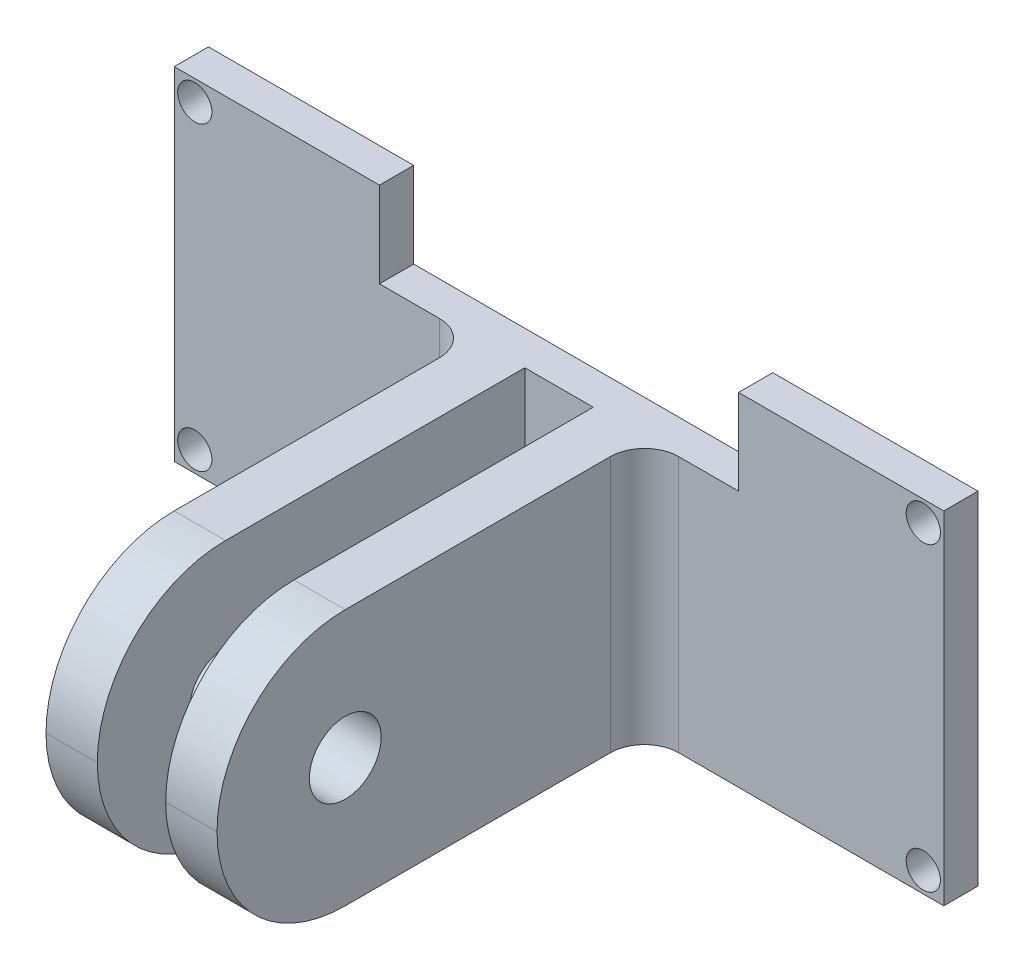
SolidWorks part; units mm, degrees
ref_plane "前视基准面" through (0, 0, 0) normal (0, 0, 1) x (1, 0, 0)
ref_plane "上视基准面" through (0, 0, 0) normal (0, 1, 0) x (1, 0, 0)
ref_plane "右视基准面" through (0, 0, 0) normal (1, 0, 0) x (0, 0, -1)
sketch "草图1" plane through (0, 0, 0) normal (0, 0, 1) x (1, 0, 0)
  line L0 (1.4667, 10.9333) -> (13.4667, 10.9333)
  line L2 (-31.5333, 10.9333) -> (-19.5333, 10.9333)
  line L3 (-31.5333, 10.9333) -> (-31.5333, -9.0667)
  line L4 (-31.5333, -9.0667) -> (13.4667, -9.0667)
  line L5 (13.4667, 10.9333) -> (13.4667, -9.0667)
  line L6 (-19.5333, 10.9333) -> (-19.5333, 5.9333)
  line L7 (-19.5333, 5.9333) -> (1.4667, 5.9333)
  line L8 (1.4667, 10.9333) -> (1.4667, 5.9333)
  circle A0 centre (-30.3333, 9.7333) radius 1
  circle A1 centre (-30.3333, -7.8667) radius 1
  circle A2 centre (12.2667, 9.7333) radius 1
  circle A3 centre (12.2667, -7.8667) radius 1
  point P16 (1.4667, 8.4333)
  dimension "D11" = 2
  dimension "D12" = 2
  dimension "D13" = 2
  dimension "D14" = 2
  dimension "D1" = 45
  dimension "D2" = 20
  dimension "D3" = 1.2
  dimension "D4" = 1.2
  dimension "D5" = 1.2
  dimension "D6" = 1.2
  dimension "D7" = 1.2
  dimension "D8" = 1.2
  dimension "D9" = 1.2
  dimension "D10" = 1.2
  dimension "D15" = 12
  dimension "D16" = 12
extrude "凸台-拉伸1" add sketch "草图1" along normal blind 2
sketch "草图2" plane through (0, 0, 2) normal (0, 0, 1) x (1, 0, 0)
  line L2 (-14.0333, 5.9333) -> (-14.0333, -9.0667)
  line L3 (-14.0333, -9.0667) -> (-11.0333, -9.0667)
  line L4 (-11.0333, 5.9333) -> (-11.0333, -9.0667)
  line L5 (-31.5333, -9.0667) -> (13.4667, -9.0667) construction
  line L6 (-31.5333, 10.9333) -> (-31.5333, -9.0667) construction
  line L8 (-7.0333, 5.9333) -> (-7.0333, -9.0667)
  line L9 (-7.0333, -9.0667) -> (-4.0333, -9.0667)
  line L10 (-4.0333, 5.9333) -> (-4.0333, -9.0667)
  line L12 (-14.0333, 5.9333) -> (-11.0333, 5.9333)
  line L13 (1.4667, 5.9333) -> (-19.5333, 5.9333) construction
  line L14 (-7.0333, 5.9333) -> (-4.0333, 5.9333)
  dimension "D1" = 3
  dimension "D2" = 3
  dimension "D3" = 4
  dimension "D4" = 17.5
extrude "凸台-拉伸2" add sketch "草图2" along normal blind 25
fillet "圆角1" radius 7.5 4 edges at (-5.5333, -9.0667, 27) (-12.5333, -9.0667, 27) (-5.5333, 5.9333, 27) (-12.5333, 5.9333, 27)
sketch "草图3" plane through (-4.0333, 0, 0) normal (1, 0, 0) x (0, 0, -1)
  circle A0 centre (-19.5, -1.5667) radius 2.1
  dimension "D1" = 4.2
extrude "切除-拉伸1" cut sketch "草图3" against normal blind 15
fillet "圆角2" radius 2 2 edges at (-4.0333, -1.5667, 2) (-14.0333, -1.5667, 2)
